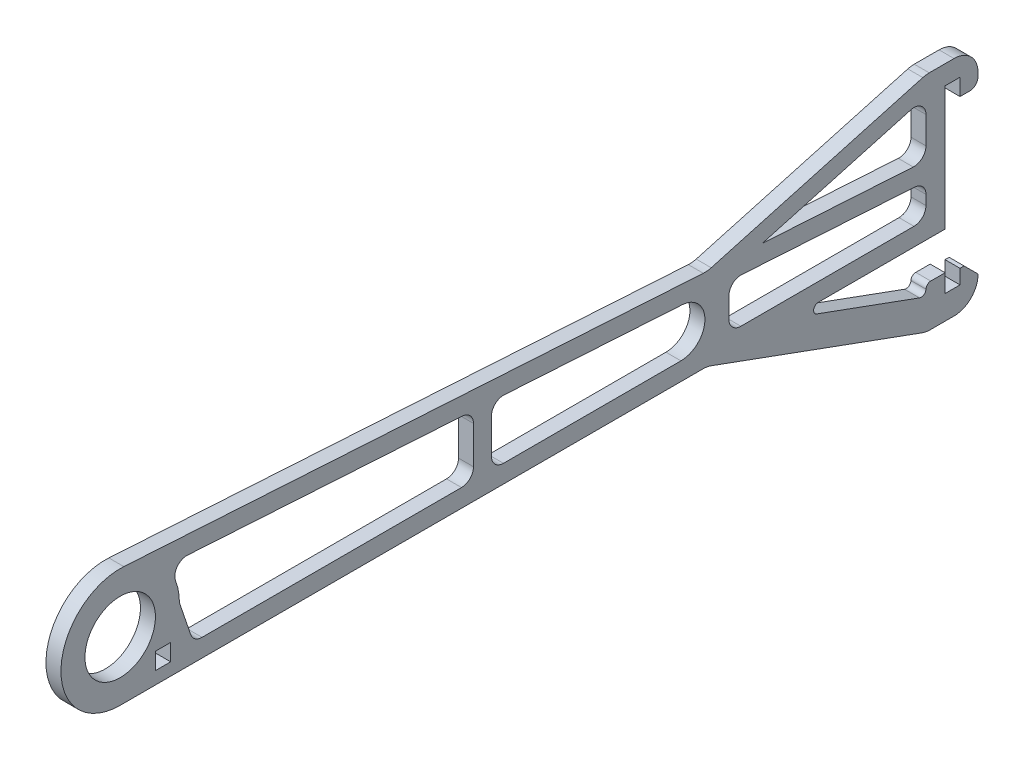
SolidWorks part; units mm, degrees
material "Delrin"
ref_plane "Front Plane" through (0, 0, 0) normal (0, 0, 1) x (1, 0, 0)
ref_plane "Top Plane" through (0, 0, 0) normal (0, 1, 0) x (1, 0, 0)
ref_plane "Right Plane" through (0, 0, 0) normal (1, 0, 0) x (0, 0, -1)
sketch "Sketch1" plane through (0, 0, 0) normal (1, 0, 0) x (0, 0, -1)
  line L0 (0.3859, 6.2619) -> (62.1851, 2.453)
  line L1 (0, -6.2738) -> (62.1851, -6.2738)
  line L2 (85.344, 8.8996) -> (88.3158, 8.8996)
  line L3 (4.7629, 4.0835) -> (85.344, -0.883)
  line L4 (4.5027, -4.3688) -> (85.344, -4.3688)
  line L5 (4.101, 4.1243) -> (87.7175, -1.0293) construction
  line L6 (0, -4.3688) -> (85.344, -4.3688) construction
  line L7 (85.344, -6.2738) -> (85.344, 8.8996) construction
  line L16 (6.2738, 0) -> (7.7597, -4.3688)
  line L17 (39.3251, 1.9533) -> (39.3251, -4.3688)
  line L18 (37.4201, 2.0707) -> (37.4201, -4.3688)
  line L23 (4.2182, 6.0257) -> (87.8347, 0.8721) construction
  line L24 (89.9668, 5.0896) -> (88.9508, 5.0896)
  line L25 (88.9508, 5.0896) -> (88.9508, 6.8676)
  line L26 (88.9508, 6.8676) -> (87.376, 6.8676)
  line L27 (87.376, 6.8676) -> (87.376, -6.2738)
  line L28 (87.376, -12.1824) -> (88.9508, -12.1824)
  line L29 (88.9508, -12.1824) -> (88.9508, -10.6584)
  line L30 (88.9508, -10.6584) -> (89.3826, -10.6584)
  line L31 (90.8558, -12.1316) -> (90.8558, -12.1824)
  line L32 (88.3158, -14.7224) -> (85.344, -14.7224)
  line L33 (85.344, -14.7224) -> (85.344, -6.2738) construction
  line L34 (90.8558, 5.9786) -> (90.8558, 6.3596)
  line L35 (89.3826, -10.6584) -> (90.8558, -12.1316)
  line L36 (64.4711, 0.4035) -> (64.4711, -4.3688)
  line L37 (62.1851, 0.5444) -> (62.1851, -4.3688)
  line L38 (62.1851, 2.453) -> (85.344, 8.8996)
  line L39 (68.0011, 2.0945) -> (85.344, 6.9222)
  line L40 (62.1851, -6.2738) -> (85.344, -14.7224)
  line L41 (71.0788, -6.2738) -> (85.344, -11.4779)
  line L42 (63.2297, -3.4104) -> (86.3886, -11.859) construction
  line L43 (62.696, 0.6178) -> (85.8549, 7.0644) construction
  line L44 (71.0788, -6.2738) -> (85.344, -6.2738)
  line L45 (0, -6.2738) -> (85.344, -6.2738) construction
  line L46 (68.0011, 2.0945) -> (85.344, 1.0256)
  line L47 (62.1851, -4.3688) -> (62.1851, 49995.6312) construction
  line L48 (85.344, 6.9222) -> (85.344, 1.0256)
  line L49 (85.344, -0.883) -> (85.344, -4.3688)
  line L50 (87.376, -12.1824) -> (87.376, -10.2774)
  line L51 (85.344, -6.2738) -> (87.376, -6.2738)
  line L52 (87.376, -10.2774) -> (85.344, -10.2774)
  line L53 (85.344, -10.2774) -> (85.344, -11.4779)
  circle A0 centre (0, 0) radius 3.7338
  circle A1 centre (0, 0) radius 6.2738
  arc A2 (88.3158, 8.8996) -> (90.8558, 6.3596) centre (88.3158, 6.3596) cw
  arc A3 (90.8558, -12.1824) -> (88.3158, -14.7224) centre (88.3158, -12.1824) cw
  arc A4 (90.8558, 5.9786) -> (89.9668, 5.0896) centre (89.9668, 5.9786) cw
  point P47 (90.8558, 8.8996)
  point P50 (90.8558, -14.7224)
  point P53 (90.8558, 5.0896)
  point P54 (90.8558, -10.6584)
  point P56 (90.8558, -10.6584)
  dimension "D1" = 7.4676
  dimension "D2" = 2.54
  dimension "D3" = 5.842
  dimension "D8" = 1.5748
  dimension "D18" = 2.54
  dimension "D19" = 2.54
  dimension "D20" = 0.889
  dimension "D21" = 22.86
  dimension "D5" = 37.4201
  dimension "D10" = 1.905
  dimension "D11" = 1.778
  dimension "D12" = 1.905
  dimension "D4" = 5.3842
  dimension "D9" = 1.5748
  dimension "D14" = 1.524
  dimension "D15" = 3.81
  dimension "D16" = 4.064
  dimension "D17" = 1.905
  dimension "D22" = 19.05
  dimension "D23" = 85.344
  dimension "D24" = 2.032
  dimension "D25" = 2.286
  dimension "D29" = 1.905
  dimension "D6" = 1.905
  dimension "D7" = 1.905
  dimension "D27" = 3.048
  dimension "D28" = 1.905
extrude "Boss-Extrude1" add sketch "Sketch1" along normal blind 1.5875 contours A1 L1 | A1 L4 L16 | L3 L18 L4 L17 | L31 L30 L29 L28 L27 L26 L25 L24 A4 L34 A2 L2 L7 L33 L32 A3 | A1 A0 | L3 L37 L4 L36 region at (0, 3.4205, -31.2278) region at (0, 5.4578, -2.7163) region at (0, -1.1783, -38.3697) region at (0, -3.082, -6.3381) region at (0, -1.9473, -63.3226)
fillet "Fillet1" radius 2.54 4 edges at (0.7937, 2.453, -62.1851) (0.7937, 8.8996, -85.344) (0.7937, -6.2738, -62.1851) (0.7937, -14.7224, -85.344)
fillet "Fillet2" radius 1.27 12 edges at (0.7937, 4.0835, -4.7629) (0.7937, -4.3688, -7.7597) (0.7937, -4.3688, -37.4201) (0.7937, 2.0707, -37.4201) (0.7937, -4.3688, -39.3251) (0.7937, 1.9533, -39.3251) (0.7937, 0.4035, -64.4711) (0.7937, -4.3688, -64.4711) (0.7937, 1.0256, -85.344) (0.7937, 6.9222, -85.344) (0.7937, -0.883, -85.344) (0.7937, -4.3688, -85.344)
fillet "Fillet3" radius 0.508 2 edges at (0.7937, -6.2738, -71.0788) (0.7937, -11.4779, -85.344)
fillet "Fillet4" radius 0.508 1 edges at (0.7937, -10.2774, -85.344)
sketch "Sketch4" plane through (1.5875, 0, 0) normal (1, 0, 0) x (0, 0, -1)
  line L0 (40.6732, 1.8702) -> (62.1851, 0.5444) construction
  line L1 (62.1851, 0.5444) -> (62.1851, -4.3688) construction
  line L2 (40.5951, -4.3688) -> (62.1851, -4.3688) construction
  line L3 (59.5471, 0.707) -> (62.1851, 0.5444)
  line L4 (62.1851, 0.5444) -> (62.1851, -4.3688)
  line L5 (59.3908, -4.3688) -> (62.1851, -4.3688)
  line L6 (61.9311, -1.8285) -> (62.1851, -1.8285) construction
  line L7 (87.376, 6.8676) -> (87.376, -6.2738) construction
  line L8 (40.5951, -4.3688) -> (62.1851, -4.3688) construction
  arc A0 (59.5471, 0.707) -> (59.3908, -4.3688) centre (59.3908, -1.8285) cw
  dimension "D1" = 0.254
extrude "Boss-Extrude2" add sketch "Sketch4" against normal up to surface (1.5875 mm away) up to face at (0, -0.6692, -20.2932)
sketch "Sketch5" plane through (1.5875, 0, 0) normal (1, 0, 0) x (0, 0, -1)
  line L4 (3.7592, -3.175) -> (3.7592, -4.953)
  line L5 (3.7592, -4.953) -> (5.3467, -4.953)
  line L6 (5.3467, -4.953) -> (5.3467, -3.175)
  line L7 (5.3467, -3.175) -> (3.7592, -3.175)
  line L8 (3.7592, -3.175) -> (3.7592, -4.953)
  line L9 (3.7592, -4.953) -> (5.3467, -4.953)
  line L10 (5.3467, -4.953) -> (5.3467, -3.175)
  line L11 (5.3467, -3.175) -> (3.7592, -3.175)
  dimension "D1" = 0
extrude "Cut-Extrude1" cut sketch "Sketch5" against normal up to next
